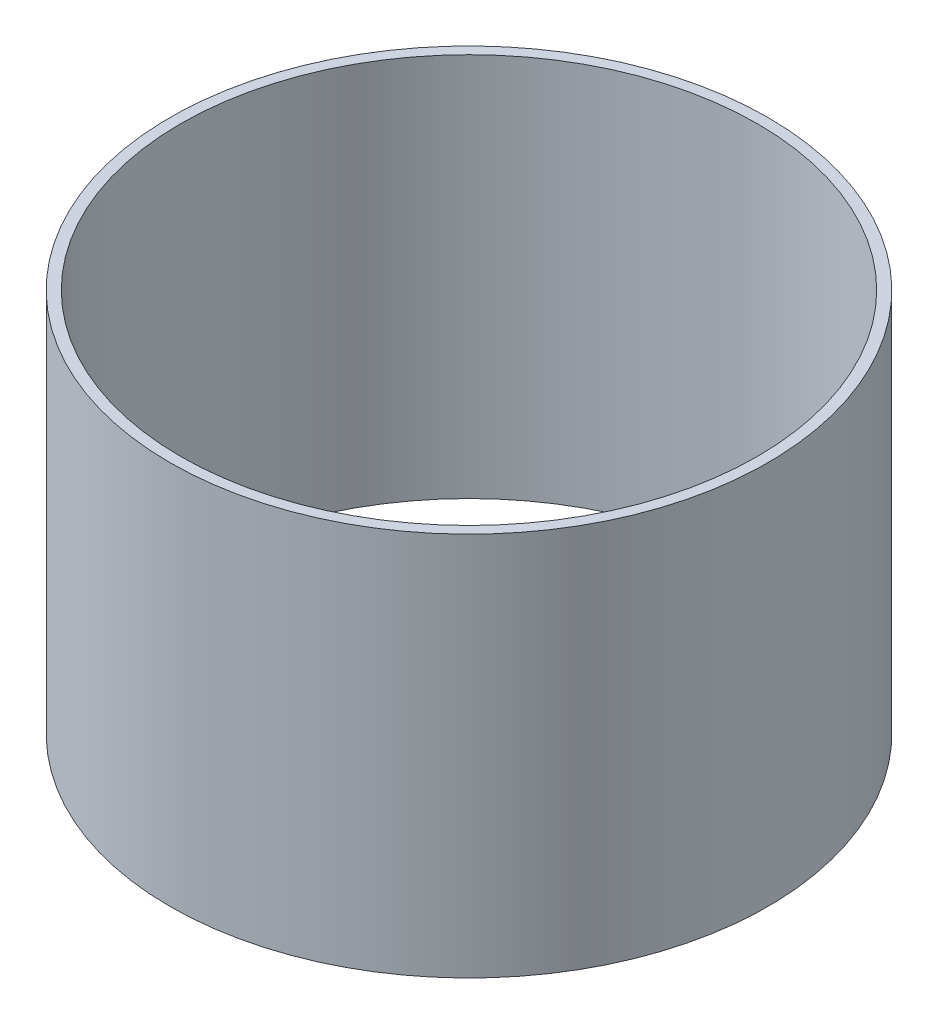
SolidWorks part; units mm, degrees
ref_plane "Front Plane" through (0, 0, 0) normal (0, 0, 1) x (1, 0, 0)
ref_plane "Top Plane" through (0, 0, 0) normal (0, 1, 0) x (1, 0, 0)
ref_plane "Right Plane" through (0, 0, 0) normal (1, 0, 0) x (0, 0, -1)
sketch "Sketch1" plane through (0, 0, 0) normal (0, 1, 0) x (1, 0, 0)
  circle A0 centre (0, 0) radius 70
  circle A1 centre (0, 0) radius 67.5
  dimension "D1" = 140
  dimension "D2" = 2.5
extrude "Boss-Extrude1" add sketch "Sketch1" along normal blind 90
